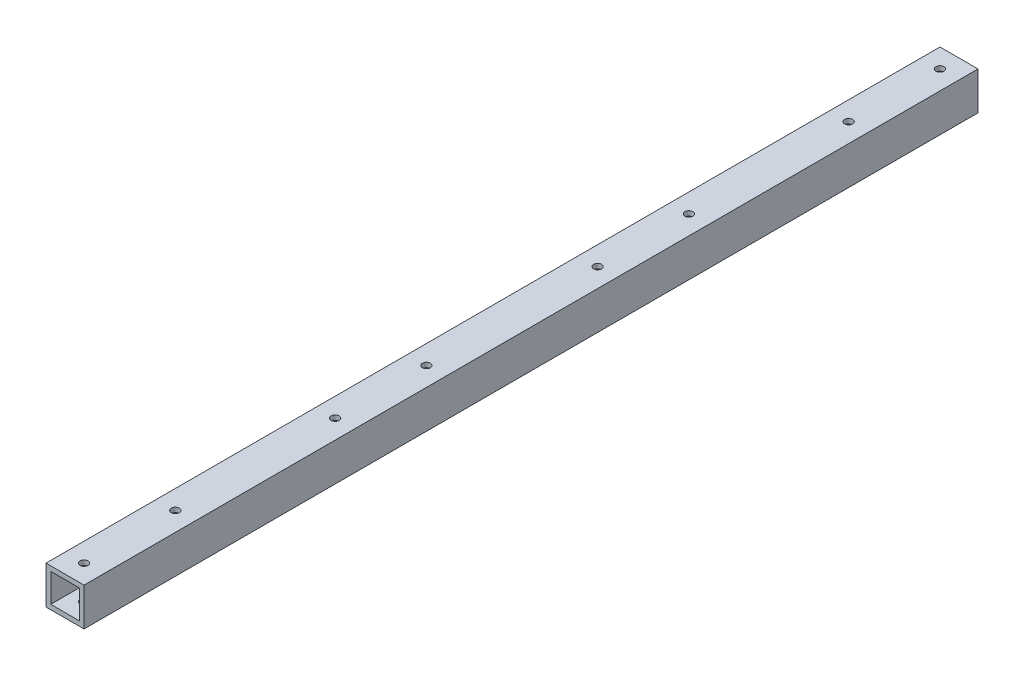
SolidWorks part; units mm, degrees
ref_plane "Front Plane" through (0, 0, 0) normal (0, 0, 1) x (1, 0, 0)
ref_plane "Top Plane" through (0, 0, 0) normal (0, 1, 0) x (1, 0, 0)
ref_plane "Right Plane" through (0, 0, 0) normal (1, 0, 0) x (0, 0, -1)
sketch "Sketch1" plane through (0, 0, 0) normal (0, 0, 1) x (1, 0, 0)
  line L0 (3.175, 22.225) -> (22.225, 22.225)
  line L1 (0, 0) -> (25.4, 0)
  line L2 (0, 0) -> (0, 25.4)
  line L3 (0, 25.4) -> (25.4, 25.4)
  line L4 (25.4, 0) -> (25.4, 25.4)
  line L5 (22.225, 3.175) -> (22.225, 22.225)
  line L6 (3.175, 3.175) -> (22.225, 3.175)
  line L7 (3.175, 3.175) -> (3.175, 22.225)
  dimension "D1" = 25.4
  dimension "D2" = 25.4
  dimension "D3" = 3.175
extrude "Boss-Extrude1" add sketch "Sketch1" along normal blind 596.9
sketch "Sketch2" plane through (0, 25.4, 0) normal (0, 1, 0) x (1, 0, 0)
  line L0 (25.4, -596.9) -> (25.4, 0) construction
  line L1 (25.4, -596.9) -> (0, -596.9) construction
  line L2 (0, -298.45) -> (25.4, -298.45) construction
  line L3 (0, -596.9) -> (0, 0) construction
  circle A0 centre (12.7, -584.2) radius 2.667
  circle A1 centre (12.7, -12.7) radius 2.667
  circle A2 centre (12.7, -523.24) radius 2.667
  circle A3 centre (12.7, -73.66) radius 2.667
  dimension "D1" = 5.334
  dimension "D4" = 5.334
  dimension "D2" = 12.7
  dimension "D3" = 12.7
  dimension "D5" = 12.7
  dimension "D6" = 73.66
extrude "Cut-Extrude1" cut sketch "Sketch2" against normal through all
sketch "Sketch4" plane through (0, 25.4, 0) normal (0, 1, 0) x (1, 0, 0)
  line L0 (0, -298.45) -> (25.4, -298.45) construction
  line L1 (0, -596.9) -> (0, 0) construction
  line L2 (25.4, -596.9) -> (25.4, 0) construction
  circle A0 centre (12.7, -416.56) radius 2.667
  circle A1 centre (12.7, -355.6) radius 2.667
  circle A2 centre (12.7, -523.24) radius 2.667 construction
  circle A4 centre (12.7, -180.34) radius 2.667
  circle A5 centre (12.7, -241.3) radius 2.667
  dimension "D1" = 106.68
  dimension "D2" = 60.96
  dimension "D5" = 5.334
  dimension "D6" = 5.334
  dimension "D3" = 12.7
  dimension "D4" = 12.7
extrude "Cut-Extrude3" cut sketch "Sketch4" against normal blind 25.4
